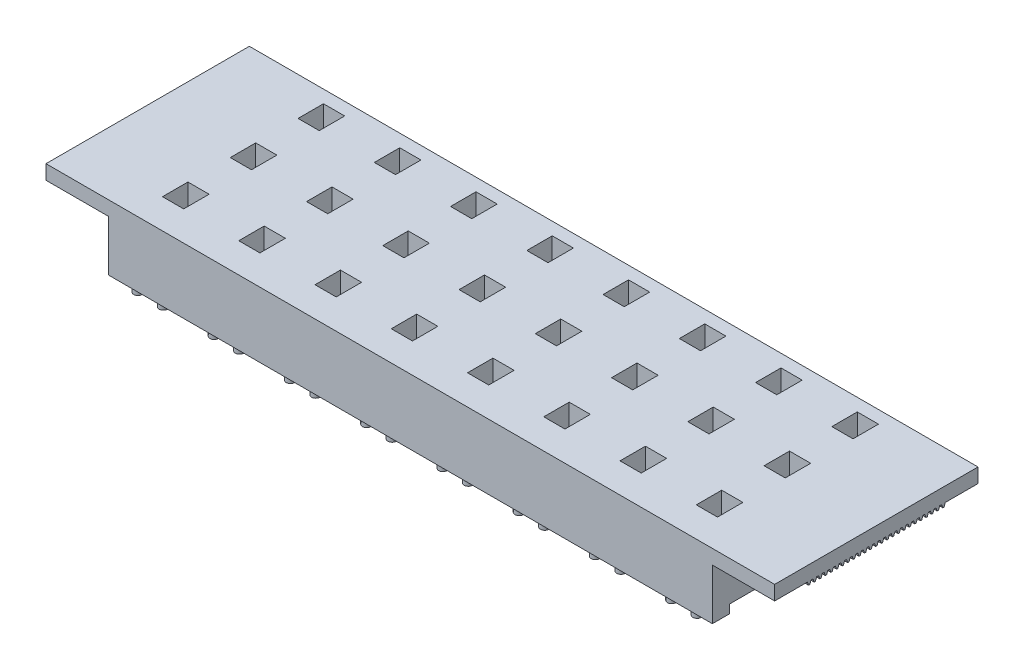
SolidWorks part; units mm, degrees
ref_plane "Front" through (0, 0, 0) normal (0, 0, 1) x (1, 0, 0)
ref_plane "Top" through (0, 0, 0) normal (0, 1, 0) x (1, 0, 0)
ref_plane "Right" through (0, 0, 0) normal (1, 0, 0) x (0, 0, -1)
sketch "Sketch1" plane through (0, 0, 0) normal (0, 1, 0) x (1, 0, 0)
  line L0 (-43, 0) -> (43, 0) construction
  line L1 (-43, 12) -> (43, 12)
  line L2 (-43, 12) -> (-43, -12)
  line L3 (-43, -12) -> (43, -12)
  line L4 (43, 12) -> (43, -12)
  line L5 (0, 12) -> (0, -12) construction
  dimension "D1" = 86
  dimension "D2" = 24
extrude "Boss-Extrude1" add sketch "Sketch1" along normal blind 6.7
sketch "Sketch2" plane through (0, 0, 12) normal (0, 0, 1) x (1, 0, 0)
  line L0 (0, 0) -> (0, 23.2403) construction
  line L1 (-43, 0) -> (43, 0) construction
  line L3 (43, 0) -> (35.65, 0)
  line L4 (43, 0) -> (43, 5)
  line L5 (43, 5) -> (35.65, 5)
  line L6 (35.65, 0) -> (35.65, 5)
  dimension "D1" = 35.65
  dimension "D2" = 5
extrude "Cut-Extrude1" cut sketch "Sketch2" against normal through all
mirror "Mirror1" about plane through (0, 0, 0) normal (1, 0, 0) of "Cut-Extrude1"
sketch "Sketch4" plane through (43, 0, 0) normal (1, 0, 0) x (0, 0, -1)
  line L0 (0, 5) -> (0, -1.3359) construction
  line L1 (12, 5) -> (-12, 5) construction
  line L10 (0, 5) -> (-3.1142, 5) construction
  line L11 (0.2206, 5) -> (-0.2206, 5)
  line L12 (0.075, 4.6) -> (0.2206, 5)
  line L13 (-0.075, 4.6) -> (0.075, 4.6)
  line L14 (-0.2206, 5) -> (-0.075, 4.6)
  line L15 (12, 5) -> (-12, 5) construction
  point P5 (0, 5)
  point P8 (0, 4.6)
  dimension "D1" = 0.4
  dimension "D2" = 40
  dimension "D4" = 0.15
extrude "First Ridge" add sketch "Sketch4" against normal up to surface (7.35 mm away) up to face at (35.65, 2.5, 0)
pattern_linear "Rack Left Pattern" count 13 spacing 0.66 along (0, 0, 1) count 13 spacing 0.66 along (0, 0, -1) of "First Ridge" pattern seed only yes
mirror "Mirror2" about plane through (0, 0, 0) normal (1, 0, 0) of "Rack Left Pattern"
sketch "Sketch5" plane through (-35.65, 0, 0) normal (-1, 0, 0) x (0, 0, 1)
  line L0 (-12, 0) -> (12, 0) construction
  line L1 (-6, 0) -> (-4, 0)
  line L2 (-6, 0) -> (-6, -1)
  line L3 (-6, -1) -> (-4, -1)
  line L4 (-4, 0) -> (-4, -1)
  line L5 (-12, 5) -> (-12, 0) construction
  line L7 (2, 0) -> (4, 0)
  line L8 (2, 0) -> (2, -1)
  line L9 (2, -1) -> (4, -1)
  line L10 (4, 0) -> (4, -1)
  line L11 (12, 0) -> (10, 0)
  line L12 (12, 0) -> (12, -1)
  line L13 (12, -1) -> (10, -1)
  line L14 (10, 0) -> (10, -1)
  dimension "D1" = 1
  dimension "D2" = 2
  dimension "D3" = 6
  dimension "D4" = 2
  dimension "D5" = 2
  dimension "D6" = 6
  dimension "D7" = 6
extrude "Boss-Extrude2" add sketch "Sketch5" against normal up to surface (71.3 mm away) up to face at (35.65, 4.7115, 0)
sketch "Sketch6" plane through (0, -1, 0) normal (0, -1, 0) x (1, 0, 0)
  line L0 (-35.65, -5) -> (-25.068, -5) construction
  line L1 (-35.65, -6) -> (-35.65, -4) construction
  circle A0 centre (-33.15, -5) radius 0.5
  circle A1 centre (-30.15, -5) radius 0.5
  dimension "D1" = 1
  dimension "D3" = 1
  dimension "D2" = 2.5
  dimension "D4" = 3
extrude "Boss-Extrude3" add sketch "Sketch6" along normal blind 1
pattern_linear "LPattern1" count 8 spacing 9 along (1, 0, 0) of "Boss-Extrude3"
pattern_linear "LPattern2" count 3 spacing 8 along (0, 0, 1) of "LPattern1"
sketch "Sketch8" plane through (0, 0, 0) normal (0, -1, 0) x (1, 0, 0)
  line L0 (0, 10) -> (0, 4) construction
  line L3 (35.65, 4) -> (-35.65, 4) construction
  line L4 (-6.5, 9.25) -> (-2.5, 9.25)
  line L5 (-6.5, 9.25) -> (-6.5, 4.75)
  line L6 (-6.5, 4.75) -> (-2.5, 4.75)
  line L7 (-2.5, 9.25) -> (-2.5, 4.75)
  line L8 (35.65, 10) -> (-35.65, 10) construction
  line L9 (0, 7) -> (4.4638, 7) construction
  line L10 (-5.75, 8.5) -> (-3.25, 8.5)
  line L11 (-3.25, 8.5) -> (-3.25, 5.5)
  line L12 (-5.75, 5.5) -> (-3.25, 5.5)
  line L13 (-5.75, 8.5) -> (-5.75, 5.5)
  point P2 (-2.5, 7)
  dimension "D1" = 2.5
  dimension "D2" = 4
  dimension "D3" = 4.5
  dimension "D4" = 0.75
extrude "Boss-Extrude4" add sketch "Sketch8" along normal up to surface (2 mm away)
sketch "Sketch9" plane through (0, 0, 0) normal (0, -1, 0) x (1, 0, 0)
  line L4 (-3.25, 5.5) -> (-3.25, 8.5)
  line L5 (-3.25, 8.5) -> (-5.75, 8.5)
  line L6 (-5.75, 8.5) -> (-5.75, 5.5)
  line L7 (-5.75, 5.5) -> (-3.25, 5.5)
  line L8 (-3.25, 5.5) -> (-3.25, 8.5)
  line L9 (-3.25, 8.5) -> (-5.75, 8.5)
  line L10 (-5.75, 8.5) -> (-5.75, 5.5)
  line L11 (-5.75, 5.5) -> (-3.25, 5.5)
  dimension "D1" = 0
extrude "Cut-Extrude2" cut sketch "Sketch9" against normal through all
pattern_linear "LPattern3" count 4 spacing 9 along (-1, 0, 0) count 5 spacing 9 along (1, 0, 0) of "Cut-Extrude2", "Boss-Extrude4" pattern seed only yes
pattern_linear "LPattern4" count 3 spacing 8 along (0, 0, -1) of "LPattern3"
